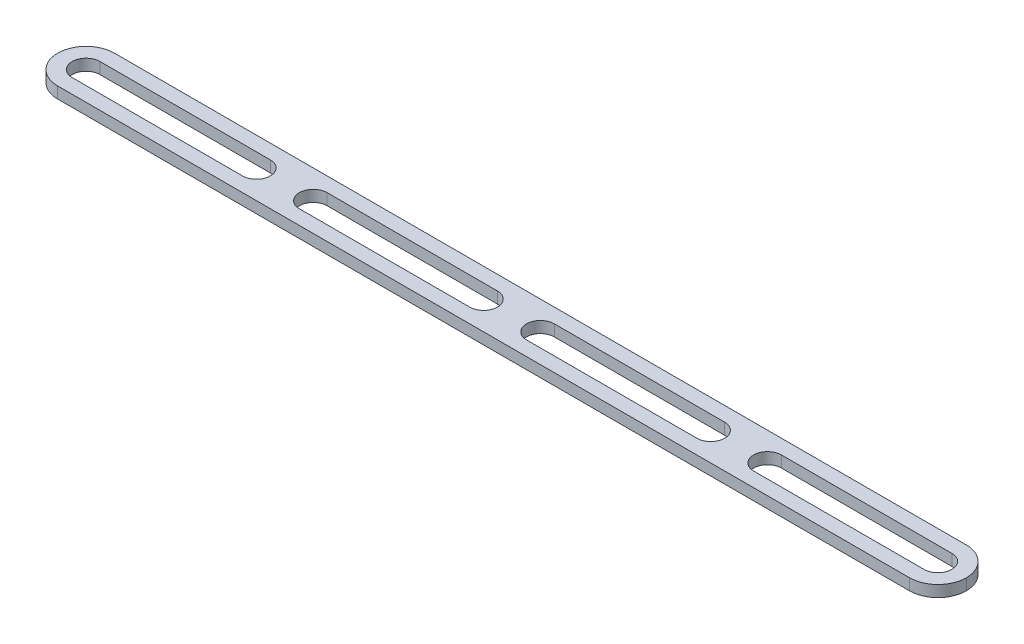
SolidWorks part; units mm, degrees
ref_plane "정면" through (0, 0, 0) normal (0, 0, 1) x (1, 0, 0)
ref_plane "윗면" through (0, 0, 0) normal (0, 1, 0) x (1, 0, 0)
ref_plane "우측면" through (0, 0, 0) normal (1, 0, 0) x (0, 0, -1)
sketch "스케치1" plane through (0, 0, 0) normal (0, 1, 0) x (1, 0, 0)
  line L1 (0, 0) -> (160, 0)
  line L2 (0, 0) -> (0, 10)
  line L3 (0, 10) -> (160, 10)
  line L4 (160, 0) -> (160, 10)
  dimension "D1" = 160
  dimension "D2" = 10
extrude "보스-돌출1" add sketch "스케치1" along normal blind 2
fillet "필렛1" radius 5 4 edges at (0, 1, 0) (0, 1, -10) (160, 1, -10) (160, 1, 0)
sketch "스케치2" plane through (0, 2, 0) normal (0, 1, 0) x (1, 0, 0)
  line L0 (5, 5) -> (35, 5) construction
  line L1 (5, 7.45) -> (35, 7.45)
  line L2 (5, 2.55) -> (35, 2.55)
  line L3 (45, 5) -> (35, 5) construction
  line L4 (85, 5) -> (75, 5) construction
  line L5 (125, 5) -> (115, 5) construction
  line L6 (45, 5) -> (75, 5) construction
  line L7 (45, 7.45) -> (75, 7.45)
  line L8 (45, 2.55) -> (75, 2.55)
  line L9 (85, 5) -> (115, 5) construction
  line L10 (85, 7.45) -> (115, 7.45)
  line L11 (85, 2.55) -> (115, 2.55)
  line L12 (125, 5) -> (155, 5) construction
  line L13 (125, 7.45) -> (155, 7.45)
  line L14 (125, 2.55) -> (155, 2.55)
  line L15 (5, 5) -> (0, 5) construction
  arc A0 (5, 7.45) -> (5, 2.55) centre (5, 5) ccw
  arc A1 (35, 2.55) -> (35, 7.45) centre (35, 5) ccw
  arc A4 (45, 7.45) -> (45, 2.55) centre (45, 5) ccw
  arc A5 (75, 2.55) -> (75, 7.45) centre (75, 5) ccw
  arc A6 (85, 7.45) -> (85, 2.55) centre (85, 5) ccw
  arc A7 (115, 2.55) -> (115, 7.45) centre (115, 5) ccw
  arc A8 (125, 7.45) -> (125, 2.55) centre (125, 5) ccw
  arc A9 (155, 2.55) -> (155, 7.45) centre (155, 5) ccw
  point P2 (20, 5)
  point P14 (60, 5)
  point P21 (100, 5)
  point P28 (140, 5)
  dimension "D4" = 2.45
  dimension "D1" = 30
  dimension "D2" = 5
  dimension "D3" = 5
extrude "컷-돌출1" cut sketch "스케치2" against normal blind 10
